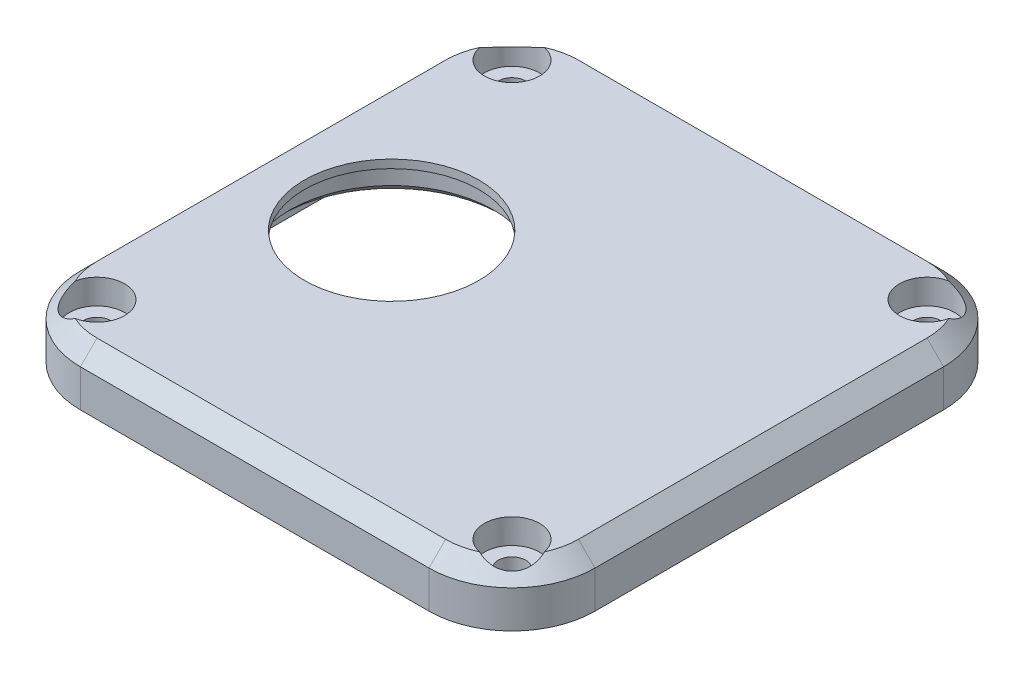
SolidWorks part; units mm, degrees
material "ABS"
ref_plane "Alzado" through (0, 0, 0) normal (0, 0, 1) x (1, 0, 0)
ref_plane "Planta" through (0, 0, 0) normal (0, 1, 0) x (1, 0, 0)
ref_plane "Vista lateral" through (0, 0, 0) normal (1, 0, 0) x (0, 0, -1)
sketch "Croquis1" plane through (0, 0, 0) normal (0, 1, 0) x (1, 0, 0)
  line L0 (0, 31) -> (62, 31)
  line L1 (62, -31) -> (0, -31)
  line L2 (62, 31) -> (62, -31)
  line L3 (0, 31) -> (0, -31)
  point P4 (0, 0)
  dimension "D1" = 62
  dimension "D2" = 62
extrude "Saliente-Extruir1" add sketch "Croquis1" along normal blind 6.5
fillet "Redondeo1" radius 10 2 edges at (62, 3.25, -31) (62, 3.25, 31)
fillet "Redondeo2" radius 10 2 edges at (0, 3.25, 31) (0, 3.25, -31)
shell "Vaciado1" thickness 2.5 removed face at (31, 6.5, 0) removed face at (31, 0, 0)
sketch "Croquis4" plane through (0, 6.5, 0) normal (0, -1, 0) x (1, 0, 0)
  line L0 (10, 28.5) -> (52, 28.5) construction
  line L1 (7.0857, 28.5) -> (54.5, 28.5)
  line L2 (2.0857, 23.5) -> (2.0857, -23.5)
  line L3 (7.0857, -28.5) -> (54.5, -28.5)
  line L4 (59.5, 23.5) -> (59.5, -23.5)
  line L5 (52, -28.5) -> (10, -28.5) construction
  line L6 (59.5, 21) -> (59.5, -21) construction
  arc A2 (54.5, 28.5) -> (59.5, 23.5) centre (54.5, 23.5) cw
  arc A3 (54.5, -28.5) -> (59.5, -23.5) centre (54.5, -23.5) ccw
  arc A4 (2.0857, -23.5) -> (7.0857, -28.5) centre (7.0857, -23.5) ccw
  arc A5 (7.0857, 28.5) -> (2.0857, 23.5) centre (7.0857, 23.5) ccw
  dimension "D1" = 5
  dimension "D2" = 5
extrude "Saliente-Extruir2" add sketch "Croquis4" along normal blind 5
sketch "Croquis6" plane through (0, 1.5, 0) normal (0, -1, 0) x (-1, 0, 0)
  line L1 (-59.5, -21) -> (-59.5, 21) construction
  circle A0 centre (-16.5, 0) radius 12.25
  dimension "D1" = 24.5
  dimension "D2" = 43
extrude "Cortar-Extruir4" cut sketch "Croquis6" against normal blind 4
sketch "Croquis7" plane through (0, 0, 0) normal (0, 1, 0) x (1, 0, 0)
  circle A0 centre (16.5, 0) radius 12.25
sketch "Croquis8" plane through (0, 5.5, 0) normal (0, -1, 0) x (1, 0, 0)
  circle A0 centre (16.5, 0) radius 10.5
  circle A1 centre (16.5, 0) radius 12.25 construction
  dimension "D1" = 1.75
extrude "Cortar-Extruir7" cut sketch "Croquis8" against normal through all
sketch "Croquis9" plane through (0, 0, 0) normal (0, -1, 0) x (1, 0, 0)
  line L0 (10, 31) -> (52, 31) construction
  line L1 (6, 25) -> (56, 25) construction
  line L2 (6, 25) -> (6, -25) construction
  line L3 (6, -25) -> (56, -25) construction
  line L4 (56, 25) -> (56, -25) construction
  line L5 (0, -21) -> (0, 21) construction
  circle A0 centre (6, 25) radius 1.65
  circle A1 centre (56, 25) radius 1.65
  circle A2 centre (56, -25) radius 1.65
  circle A3 centre (6, -25) radius 1.65
  point P9 (6, 0)
  dimension "D1" = 3.3
  dimension "D2" = 50
  dimension "D3" = 6
  dimension "D4" = 6
extrude "Cortar-Extruir8" cut sketch "Croquis9" against normal through all
sketch "Croquis10" plane through (0, 6.5, 0) normal (0, 1, 0) x (1, 0, 0)
  circle A0 centre (6, 25) radius 3.325
  circle A1 centre (6, -25) radius 3.325
  circle A2 centre (56, -25) radius 3.325
  circle A3 centre (56, 25) radius 3.325
  dimension "D1" = 6.65
extrude "Cortar-Extruir9" cut sketch "Croquis10" against normal blind 3
sketch "Croquis11" plane through (0, 1.5, 0) normal (0, -1, 0) x (1, 0, 0)
  circle A0 centre (6, 25) radius 3.91
  circle A1 centre (6, -25) radius 3.7949
  circle A2 centre (56, -25) radius 3.5969
  circle A3 centre (56, 25) radius 3.5969
  circle A4 centre (56, -25) radius 1.65
  circle A5 centre (6, -25) radius 1.65
  circle A6 centre (6, 25) radius 1.65
  circle A7 centre (56, 25) radius 1.65
  circle A8 centre (56, 25) radius 1.65 construction
  circle A9 centre (6, 25) radius 1.65 construction
  circle A10 centre (56, -25) radius 1.65 construction
  circle A11 centre (6, -25) radius 1.65 construction
extrude "Saliente-Extruir3" add sketch "Croquis11" along normal up to surface (1.5 mm away) up to face at (31, 0, 0)
fillet "Redondeo3" radius 2 8 edges at (54.2639, 0.75, 28.1502) (59.1502, 0.75, 23.2639) (59.1502, 0.75, -23.2639) (54.2639, 0.75, -28.1502) (2.7726, 0.75, -23.0037) (7.9963, 0.75, -28.2274) (2.7324, 0.75, 22.8526) (8.1474, 0.75, 28.2676)
chamfer "Chaflán1" distance 1 angle 45 1 edges at (16.5, 1.5, -12.25)
chamfer "Chaflán2" distance 2 angle 45 8 edges at (0, 6.5, 0) (2.9289, 6.5, 28.0711) (2.9289, 6.5, -28.0711) (31, 6.5, 31) (31, 6.5, -31) (59.0711, 6.5, 28.0711) (59.0711, 6.5, -28.0711) (62, 6.5, 0)
sketch "Croquis12" plane through (0, 1.5, 0) normal (0, -1, 0) x (1, 0, 0)
  circle A0 centre (44, 0) radius 5.75
  point P2 (0, 0)
  dimension "D1" = 11.5
  dimension "D2" = 44
extrude "Cortar-Extruir10" cut sketch "Croquis12" against normal blind 4
chamfer "Chaflán3" distance 1 angle 45 1 edges at (44, 1.5, -5.75)
sketch "Croquis14" plane through (0, 1.5, 0) normal (0, -1, 0) x (1, 0, 0)
  line L0 (-13.3073, 0) -> (67.5113, 0) construction
  line L1 (20.9195, 24.8912) -> (43.4463, 24.8912)
  line L2 (44.8605, 24.3054) -> (51.3917, 17.7742)
  line L3 (51.9775, 16.36) -> (51.9775, 13.6253)
  line L4 (49.9775, 11.6253) -> (39.9862, 11.6253)
  line L5 (39.3774, 11.7202) -> (20.3107, 17.8136)
  line L6 (18.9195, 19.7187) -> (18.9195, 22.8912)
  line L7 (18.9195, -19.7187) -> (18.9195, -22.8912)
  line L8 (39.3774, -11.7202) -> (20.3107, -17.8136)
  line L9 (49.9775, -11.6253) -> (39.9862, -11.6253)
  line L10 (51.9775, -16.36) -> (51.9775, -13.6253)
  line L11 (44.8605, -24.3054) -> (51.3917, -17.7742)
  line L12 (20.9195, -24.8912) -> (43.4463, -24.8912)
  arc A0 (39.9862, 11.6253) -> (39.3774, 11.7202) centre (39.9862, 13.6253) cw
  arc A1 (51.9775, 13.6253) -> (49.9775, 11.6253) centre (49.9775, 13.6253) cw
  arc A2 (51.3917, 17.7742) -> (51.9775, 16.36) centre (49.9775, 16.36) cw
  arc A3 (43.4463, 24.8912) -> (44.8605, 24.3054) centre (43.4463, 22.8912) cw
  arc A4 (20.3107, 17.8136) -> (18.9195, 19.7187) centre (20.9195, 19.7187) cw
  arc A5 (20.9195, 24.8912) -> (18.9195, 22.8912) centre (20.9195, 22.8912) ccw
  arc A6 (20.9195, -24.8912) -> (18.9195, -22.8912) centre (20.9195, -22.8912) cw
  arc A7 (20.3107, -17.8136) -> (18.9195, -19.7187) centre (20.9195, -19.7187) ccw
  arc A8 (43.4463, -24.8912) -> (44.8605, -24.3054) centre (43.4463, -22.8912) ccw
  arc A9 (51.3917, -17.7742) -> (51.9775, -16.36) centre (49.9775, -16.36) ccw
  arc A10 (51.9775, -13.6253) -> (49.9775, -11.6253) centre (49.9775, -13.6253) ccw
  arc A11 (39.9862, -11.6253) -> (39.3774, -11.7202) centre (39.9862, -13.6253) ccw
  dimension "D1" = 2
extrude "Cortar-Extruir11" cut sketch "Croquis14" against normal blind 3
chamfer "Chaflán4" distance 2 angle 45 24 edges at (48.1261, 1.5, -21.0398) (51.8253, 1.5, -17.1253) (44.2116, 1.5, -24.739) (51.9775, 1.5, -14.9926) (32.1829, 1.5, -24.8912) (51.3917, 1.5, -12.211) (19.5053, 1.5, -24.3054) (44.9819, 1.5, -11.6253) (18.9195, 1.5, -21.305) (39.6781, 1.5, -11.6491) (19.3043, 1.5, -18.5392) (29.844, 1.5, -14.7669) (44.9819, 1.5, 11.6253) (51.3917, 1.5, 12.211) (39.6781, 1.5, 11.6491) (51.9775, 1.5, 14.9926) (29.844, 1.5, 14.7669) (51.8253, 1.5, 17.1253) (19.3043, 1.5, 18.5392) (48.1261, 1.5, 21.0398) (18.9195, 1.5, 21.305) (44.2116, 1.5, 24.739) (19.5053, 1.5, 24.3054) (32.1829, 1.5, 24.8912)
